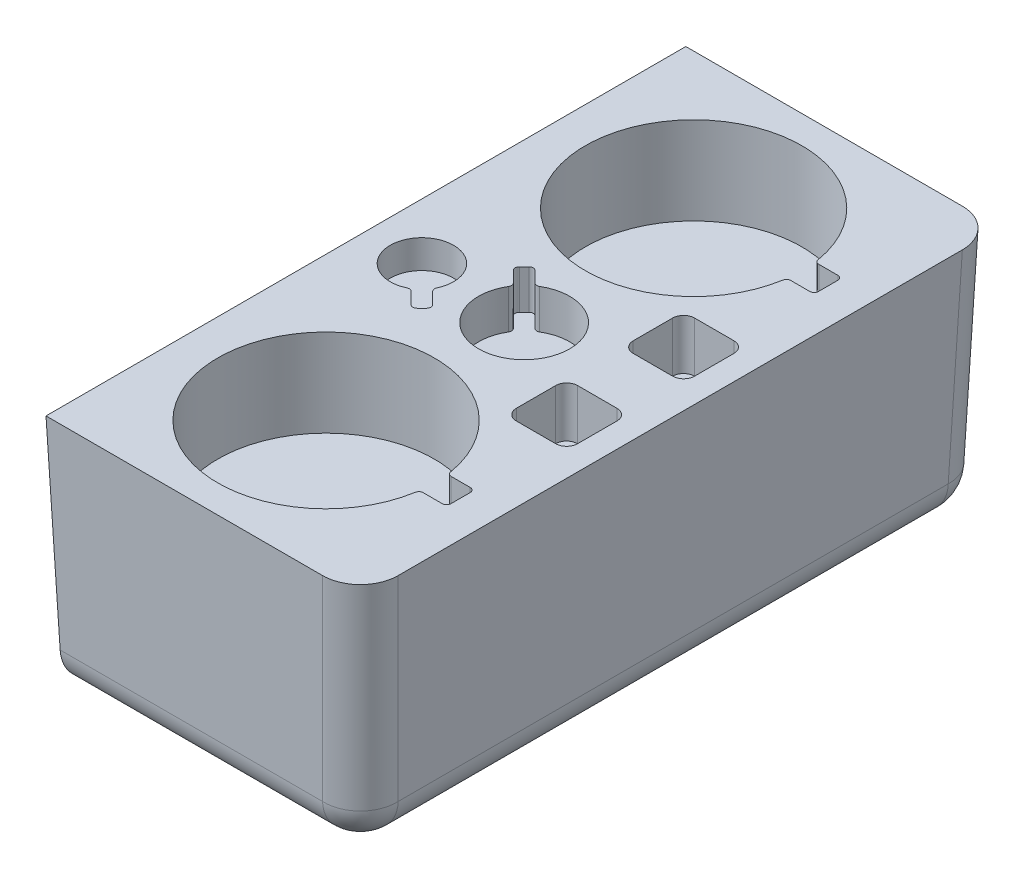
SolidWorks part; units mm, degrees
ref_plane "Front Plane" through (0, 0, 0) normal (0, 0, 1) x (1, 0, 0)
ref_plane "Top Plane" through (0, 0, 0) normal (0, 1, 0) x (1, 0, 0)
ref_plane "Right Plane" through (0, 0, 0) normal (1, 0, 0) x (0, 0, -1)
sketch "Sketch3" plane through (0, 0, 0) normal (0, 1, 0) x (1, 0, 0)
  line L1 (-67.945, -142.24) -> (67.945, -142.24)
  line L2 (-67.945, -142.24) -> (-67.945, 142.24)
  line L3 (-67.945, 142.24) -> (67.945, 142.24)
  line L4 (67.945, -142.24) -> (67.945, 142.24)
  line L5 (-67.945, -142.24) -> (67.945, 142.24) construction
  line L6 (-67.945, 142.24) -> (67.945, -142.24) construction
  point P0 (0, 0)
  dimension "D1" = 135.89
  dimension "D2" = 284.48
extrude "Boss-Extrude1" add sketch "Sketch3" along normal blind 109.22 draft 2 draft outward yes
sketch "Sketch1" plane through (0, 0, 0) normal (0, 1, 0) x (1, 0, 0)
  line L0 (42.981, 90.304) -> (55.381, 90.304)
  line L5 (55.381, 90.304) -> (55.381, 77.504)
  line L6 (55.381, 77.504) -> (42.981, 77.504)
  line L7 (42.981, -77.504) -> (55.381, -77.504)
  line L8 (55.381, -77.504) -> (55.381, -90.304)
  line L9 (55.381, -90.304) -> (42.981, -90.304)
  line L16 (37.583, 12.7) -> (55.583, 12.7)
  line L17 (32.583, 17.7) -> (32.583, 35.7)
  line L18 (37.583, 40.7) -> (55.583, 40.7)
  line L19 (60.583, 17.7) -> (60.583, 35.7)
  line L20 (32.583, 12.7) -> (60.583, 40.7) construction
  line L21 (32.583, 40.7) -> (60.583, 12.7) construction
  line L22 (37.583, -40.7) -> (55.583, -40.7)
  line L23 (32.583, -35.7) -> (32.583, -17.7)
  line L24 (37.583, -12.7) -> (55.583, -12.7)
  line L25 (60.583, -35.7) -> (60.583, -17.7)
  line L26 (32.583, -40.7) -> (60.583, -12.7) construction
  line L27 (32.583, -12.7) -> (60.583, -40.7) construction
  line L28 (-72.9829, 0) -> (73.943, 0) construction
  line L29 (71.759, 146.054) -> (-71.759, 146.054) construction
  line L31 (-71.759, 146.054) -> (-71.759, -146.054) construction
  line L34 (71.759, -146.054) -> (71.759, 146.054) construction
  line L35 (-71.759, -146.054) -> (71.759, -146.054) construction
  line L42 (-19.1092, 24.539) -> (-11.5432, 16.973)
  line L43 (-19.1092, 24.539) -> (-24.059, 19.5893)
  line L44 (-24.059, 19.5893) -> (-16.4929, 12.0232)
  line L45 (-21.5841, 22.0641) -> (0.48, 0) construction
  line L46 (-46.2054, 0) -> (-28.5137, -17.6916) construction
  line L47 (-38.7668, -12.3883) -> (-30.9886, -20.1665)
  line L48 (-30.9886, -20.1665) -> (-26.0389, -15.2167)
  line L49 (-26.0389, -15.2167) -> (-33.817, -7.4386)
  arc A0 (42.981, 90.304) -> (42.981, 77.504) centre (-6.053, 83.904) ccw
  arc A1 (42.981, -77.504) -> (42.981, -90.304) centre (-6.053, -83.904) ccw
  arc A4 (55.583, 40.7) -> (60.583, 35.7) centre (55.583, 35.7) cw
  arc A5 (55.583, 12.7) -> (60.583, 17.7) centre (55.583, 17.7) ccw
  arc A6 (37.583, 12.7) -> (32.583, 17.7) centre (37.583, 17.7) cw
  arc A7 (32.583, 35.7) -> (37.583, 40.7) centre (37.583, 35.7) cw
  arc A8 (37.583, -40.7) -> (32.583, -35.7) centre (37.583, -35.7) cw
  arc A9 (55.583, -40.7) -> (60.583, -35.7) centre (55.583, -35.7) ccw
  arc A10 (55.583, -12.7) -> (60.583, -17.7) centre (55.583, -17.7) cw
  arc A11 (32.583, -17.7) -> (37.583, -12.7) centre (37.583, -17.7) cw
  arc A12 (-33.817, -7.4386) -> (-38.7668, -12.3883) centre (-46.2054, 0) ccw
  arc A16 (-16.4929, 12.0232) -> (-11.5432, 16.973) centre (0.48, 0) ccw
  circle A17 centre (46.583, 26.7) radius 8.35
  circle A18 centre (46.583, -26.7) radius 8.35
  point P13 (46.583, 12.7)
  point P25 (46.583, 26.7)
  point P42 (46.583, -26.7)
  dimension "D3" = 98.9
  dimension "D4" = 98.9
  dimension "D8" = 20.8
  dimension "D11" = 11.303
  dimension "D15" = 5
  dimension "D18" = 5
  dimension "D5" = 12.7
  dimension "D19" = 16.256
  dimension "D20" = 12.7
  dimension "D21" = 28.9
  dimension "D22" = 135
  dimension "D23" = 7
  dimension "D25" = 12.7
  dimension "D12" = 11.1037
  dimension "D13" = 45
  dimension "D27" = 16.7
  dimension "D1" = 12.4
  dimension "D2" = 12.8
  dimension "D6" = 12.8
  dimension "D7" = 12.4
  dimension "D9" = 7
  dimension "D10" = 10.7
  dimension "D14" = 28
  dimension "D16" = 28
  dimension "D17" = 28
  dimension "D24" = 11
  dimension "D26" = 11.176
fillet "Fillet1" radius 17.272 5 edges at (0, 0, -142.24) (0, 0, 142.24) (67.945, 0, 0) (69.852, 54.61, -144.147) (69.852, 54.61, 144.147)
extrude "Cut-Extrude1" cut sketch "Sketch1" against normal blind 40 from surface contours A0 L6 L5 L0 | A1 L9 L8 L7 starting at face at (19.3579, 109.22, 0)
extrude "Cut-Extrude2" cut sketch "Sketch1<4>" against normal blind 13 from surface contours L49 A12 L47 L48 region at (-44.779, 0, 1.4263) starting at face at (24.56, 109.22, 83.904)
sketch "Sketch1<4>" plane through (0, 0, 0) normal (0, 1, 0) x (1, 0, 0) same geometry as "Sketch1"
extrude "Cut-Extrude3" cut sketch "Sketch1<5>" against normal blind 18 from surface contours L44 A16 L42 L43 region at (-0.4616, 0, -0.9416) starting at face at (-37.4356, 109.22, 8.7697)
sketch "Sketch1<5>" plane through (0, 0, 0) normal (0, 1, 0) x (1, 0, 0) same geometry as "Sketch1"
extrude "Cut-Extrude5" cut sketch "Sketch1<6>" against normal blind 23 from surface contours A7 L17 A6 L16 A5 L19 A4 L18 | A11 L23 A8 L22 A9 L25 A10 L24 region at (34.3275, 0, -14.4445) region at (34.3275, 0, 38.9555) starting at face at (-10.4996, 109.22, -10.9796)
sketch "Sketch1<6>" plane through (0, 0, 0) normal (0, 1, 0) x (1, 0, 0) same geometry as "Sketch1"
extrude "Cut-Extrude7" cut sketch "Sketch1<7>" against normal blind 31 from surface contours A17 | A18 region at (46.583, 0, -26.7) region at (46.583, 0, 26.7) starting at face at (46.583, 109.22, 26.7)
sketch "Sketch1<7>" plane through (0, 0, 0) normal (0, 1, 0) x (1, 0, 0) same geometry as "Sketch1"
fillet "Fillet2" radius 2 16 edges at (42.981, 89.22, 90.304) (42.981, 89.22, 77.504) (55.381, 89.22, 77.504) (55.381, 89.22, 90.304) (-30.9886, 102.72, 20.1665) (-26.0389, 102.72, 15.2167) (-33.817, 102.72, 7.4386) (-38.7668, 102.72, 12.3883) (-16.4929, 100.22, -12.0232) (-24.059, 100.22, -19.5893) (-19.1092, 100.22, -24.539) (-11.5432, 100.22, -16.973) (42.981, 89.22, -77.504) (55.381, 89.22, -90.304) (55.381, 89.22, -77.504) (42.981, 89.22, -90.304)
